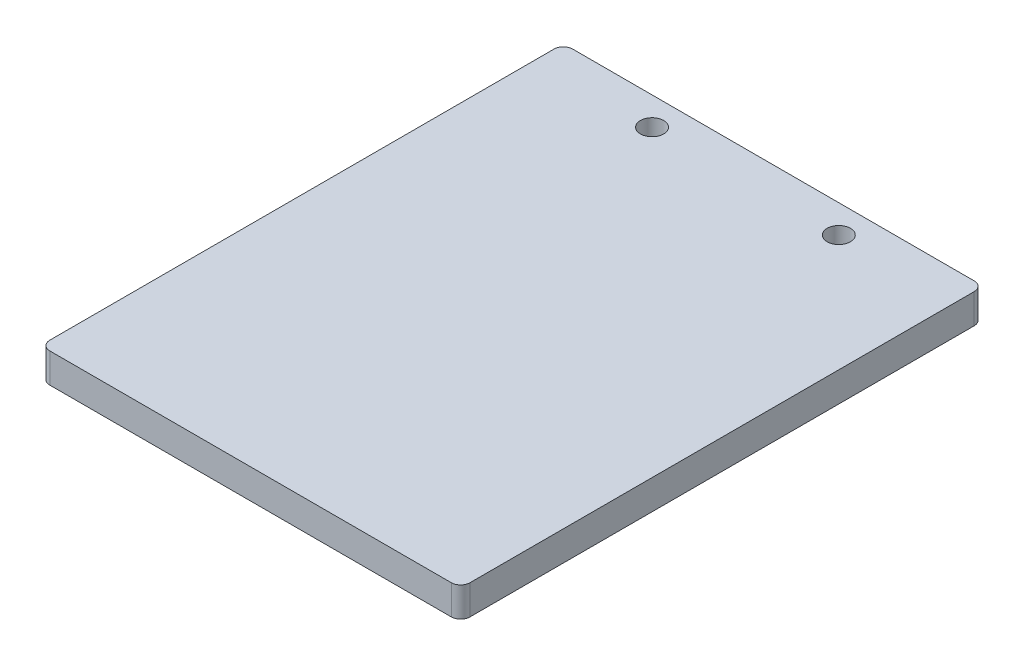
SolidWorks part; units mm, degrees
ref_plane "Front Plane" through (0, 0, 0) normal (0, 0, 1) x (1, 0, 0)
ref_plane "Top Plane" through (0, 0, 0) normal (0, 1, 0) x (1, 0, 0)
ref_plane "Right Plane" through (0, 0, 0) normal (1, 0, 0) x (0, 0, -1)
sketch "Sketch1" plane through (0, 0, 0) normal (0, 1, 0) x (1, 0, 0)
  line L1 (0, 0) -> (45, 0)
  line L2 (0, 0) -> (0, -56)
  line L3 (0, -56) -> (45, -56)
  line L4 (45, 0) -> (45, -56)
  circle A0 centre (12.5, -3) radius 1.1
  circle A1 centre (32.5, -3) radius 1.1
  point P9 (15, -2.68)
  dimension "D4" = 2.2
  dimension "D1" = 56
  dimension "D2" = 20
  dimension "D5" = 45
  dimension "D6" = 12.5
  dimension "D3" = 3
extrude "Boss-Extrude1" add sketch "Sketch1" along normal blind 3.175
fillet "Fillet1" radius 1 4 edges at (0, 1.5875, 56) (45, 1.5875, 56) (45, 1.5875, 0) (0, 1.5875, 0)
hole_wizard "M3x0.5 Tapped Hole1" positions "3DSketch1" profile "Sketch2" tap size "M3x0.5" standard "ANSI Metric" end condition through all
sketch3d "3DSketch1"
  circle A0 centre (32.5, 3.175, 3) radius 1.1 construction
  circle A1 centre (12.5, 3.175, 3) radius 1.1 construction
  point P0 (12.5, 3.175, 3)
  point P2 (32.5, 3.175, 3)
  point P7 (32.5, 4.275, 3)
  point P8 (0, 0, 0)
  point P11 (12.5, 4.275, 3)
sketch "Sketch2" plane through (12.5, 3.175, 3) normal (1, 0, 0) x (0, 0, 1)
  line L0 (0, 0) -> (0, 3.175)
  line L1 (0, 3.175) -> (1.25, 3.175)
  line L2 (1.25, 3.175) -> (1.25, 0)
  line L5 (1.25, 0) -> (0, 0)
  line L11 (0, -6.35) -> (0, 107.95) construction
  dimension "Thru Tap Drill Dia." = 2.5
  dimension "Thru Tap Drill Depth" = 3.175
cosmetic thread "Hole Thread1" parameters "D2"=3
cosmetic thread "Hole Thread2" parameters "D2"=3
equation "\"D6@Sketch1\"=(\"D5@Sketch1\"-\"D2@Sketch1\")/2"
